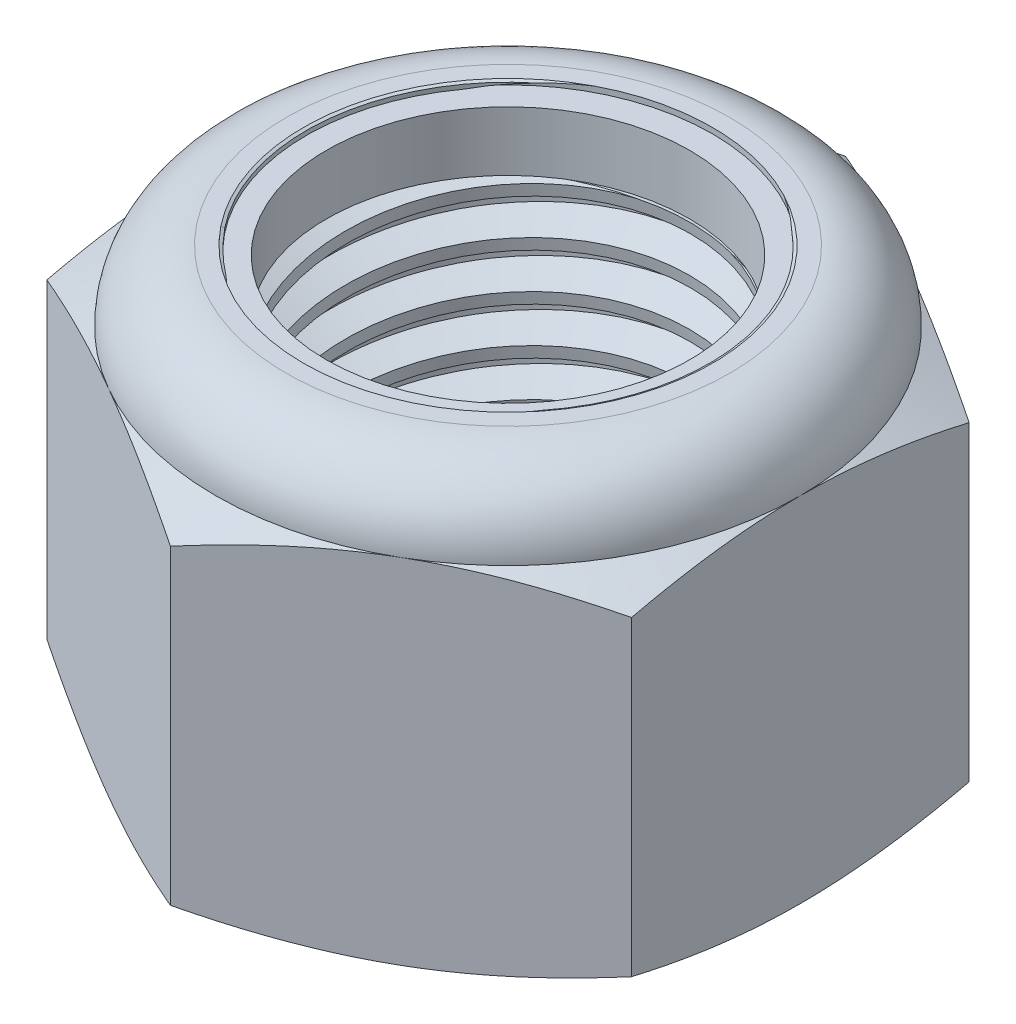
SolidWorks part; units mm, degrees
ref_plane "Front" through (0, 0, 0) normal (0, 0, 1) x (1, 0, 0)
ref_plane "Top" through (0, 0, 0) normal (0, 1, 0) x (1, 0, 0)
ref_plane "Right" through (0, 0, 0) normal (1, 0, 0) x (0, 0, -1)
sketch "Sketch1" plane through (0, 0, 0) normal (0, 1, 0) x (1, 0, 0)
  line L1 (0, 9.1654) -> (-7.9375, 4.5827)
  line L2 (-7.9375, 4.5827) -> (-7.9375, -4.5827)
  line L3 (-7.9375, -4.5827) -> (0, -9.1654)
  line L4 (0, -9.1654) -> (7.9375, -4.5827)
  line L5 (7.9375, -4.5827) -> (7.9375, 4.5827)
  line L6 (7.9375, 4.5827) -> (0, 9.1654)
  circle A0 centre (0, 0) radius 7.9375 construction
  dimension "Hex Flats" = 15.875
extrude "Extrude1" add sketch "Sketch1" along normal blind 11.5094
sketch "Sketch2" plane through (0, 0, 0) normal (1, 0, 0) x (0, 0, -1)
  line L0 (-5.5499, 0) -> (-5.5499, 11.5094) construction
  line L1 (0, 0) -> (5.5499, 0)
  line L2 (0, 0) -> (0, 11.5094)
  line L3 (0, 11.5094) -> (5.5499, 11.5094)
  line L4 (5.5499, 0) -> (5.5499, 11.5094)
  line L5 (-4.5827, 11.5094) -> (4.5827, 11.5094) construction
  line L7 (0, -5.5499) -> (0, 0) construction
  dimension "Thread Dia" = 11.0998
revolve "Revolve1" add sketch "Sketch2" angle 360 about L7
sketch "Sketch3" plane through (0, 0, 0) normal (1, 0, 0) x (0, 0, -1)
  line L0 (5.5499, 11.5094) -> (-5.5499, 11.5094) construction
  line L1 (-5.5499, 11.5094) -> (-5.5499, 10.2394) construction
  line L2 (-5.5499, 10.2394) -> (5.5499, 11.5094) construction
  line L3 (5.5499, 11.5094) -> (5.5679, 11.3517) construction
  line L4 (5.5679, 11.3517) -> (5.6943, 10.2476)
  line L5 (5.6943, 10.2476) -> (4.9662, 10.5638)
  line L6 (4.9662, 10.5638) -> (4.9301, 10.8792)
  line L7 (4.9301, 10.8792) -> (5.5679, 11.3517)
  line L8 (4.9482, 10.7215) -> (5.6311, 10.7996) construction
  line L9 (5.5499, 11.5094) -> (5.5499, 10.7903) construction
  line L10 (5.5499, 10.7903) -> (-5.5499, 9.5203) construction
  line L11 (-5.5499, 9.5203) -> (-5.5499, 10.2394) construction
  line L12 (-0.1549, 11.5094) -> (0.1549, 8.8013) construction
  line L13 (-5.5499, 0) -> (-5.5499, 11.5094) construction
  line L14 (0, 11.5094) -> (5.5499, 11.5094) construction
  line L15 (5.5499, 0) -> (5.5499, 11.5094) construction
  point P13 (0, 10.1553)
  dimension "D1" = 0.1588
  dimension "D2" = 0.3175
  dimension "Thread Pitch" = 1.27
  dimension "D4" = 60
  dimension "D5" = 1.27
revolve "Cut-Revolve1" cut sketch "Sketch3" angle 360 about L12
pattern_linear "LPattern1" count 9 spacing 1.27 along (0, -1, 0) count 2 spacing 1.27 along (0, 1, 0) of "Cut-Revolve1"
sketch "Sketch4" plane through (0, 0, 0) normal (1, 0, 0) x (0, 0, -1)
  line L0 (0, 11.5094) -> (5.5499, 11.5094)
  line L1 (5.5499, 11.5094) -> (4.9301, 11.2204)
  line L2 (4.9301, 11.2204) -> (4.9301, 0.289)
  line L3 (4.9301, 0.289) -> (5.5499, 0)
  line L4 (5.5499, 0) -> (0, 0)
  line L5 (0, 0) -> (0, 11.5094)
  line L6 (5.5499, 0) -> (5.5499, 11.5094) construction
  line L7 (0, 11.5094) -> (5.5499, 11.5094) construction
  line L8 (0, 0) -> (5.5499, 0) construction
  line L9 (0, 0) -> (0, 11.5094) construction
  line L10 (0, 11.5094) -> (0, 12.1932) construction
  dimension "D1" = 25
revolve "Cut-Revolve2" cut sketch "Sketch4" angle 360 about L10
combine bodies "Combine1" operation type subtract main body 112 bodies to subtract 111
sketch "Sketch5" plane through (0, 0, 0) normal (1, 0, 0) x (0, 0, -1)
  line L0 (0, 0) -> (7.9375, 0)
  line L1 (7.9375, 0) -> (9.1654, 0.5726)
  line L2 (9.1654, 0.5726) -> (9.1654, 9.0186)
  line L3 (9.1654, 9.0186) -> (7.9375, 9.5911)
  line L4 (6.0193, 11.5094) -> (6.0193, 12.7794)
  line L5 (6.0193, 12.7794) -> (10.4354, 12.7794)
  line L6 (10.4354, 12.7794) -> (10.4354, -1.27)
  line L7 (10.4354, -1.27) -> (0, -1.27)
  line L8 (0, -1.27) -> (0, 0)
  line L9 (7.9375, 9.5911) -> (7.9375, 0) construction
  line L10 (0, 0) -> (5.5499, 0) construction
  line L13 (9.1654, 4.7956) -> (10.4354, 4.7956) construction
  line L14 (9.1654, 11.5094) -> (9.1654, 0) construction
  line L15 (0, 0) -> (0, 12.7794) construction
  line L20 (0, 12.7794) -> (6.0193, 12.7794) construction
  line L22 (0, 11.5094) -> (5.5499, 11.5094) construction
  arc A0 (7.9375, 9.5911) -> (6.0193, 11.5094) centre (6.0193, 9.5911) ccw
  dimension "D1" = 25
  dimension "D2" = 1.27
  dimension "D3" = 11.5094
  dimension "D4" = 1.9182
revolve "Cut-Revolve3" cut sketch "Sketch5" angle 360 about L15
sketch "Sketch6" plane through (0, 0, 0) normal (1, 0, 0) x (0, 0, -1)
  line L0 (0, 9.5911) -> (7.7851, 9.5911)
  line L1 (6.0193, 11.357) -> (5.4747, 11.357)
  line L2 (0, 12.7794) -> (0, 9.5911)
  line L3 (5.4747, 12.7794) -> (0, 12.7794)
  line L4 (0, 12.7794) -> (6.0193, 12.7794) construction
  line L5 (0, 0) -> (0, 12.7794) construction
  line L6 (0, 12.7794) -> (0, 44.323) construction
  line L7 (5.4747, 11.357) -> (5.4747, 12.7794)
  line L8 (6.0193, 11.5094) -> (6.0193, 11.357) construction
  line L9 (5.4747, 11.357) -> (4.9301, 11.357) construction
  line L10 (4.9301, 11.357) -> (4.9301, 11.2204) construction
  arc A0 (7.7851, 9.5911) -> (6.0193, 11.357) centre (6.0193, 9.5911) ccw
  arc A1 (7.9375, 9.5911) -> (6.0193, 11.5094) centre (6.0193, 9.5911) ccw construction
  dimension "D1" = 0.1524
revolve "Cut-Revolve4" cut sketch "Sketch6" angle 360 about L6
sketch "Sketch7" plane through (0, 0, 0) normal (1, 0, 0) x (0, 0, -1)
  line L0 (4.9301, 9.6673) -> (7.7072, 9.6673)
  line L1 (6.0193, 11.2808) -> (4.9301, 11.2808)
  line L2 (4.9301, 11.2808) -> (4.9301, 9.6673)
  line L3 (4.9301, 9.6673) -> (0, 9.6673) construction
  line L4 (0, 9.6673) -> (0, 11.2808) construction
  line L5 (0, 11.2808) -> (4.9301, 11.2808) construction
  line L6 (4.9301, 9.6673) -> (4.9301, 9.5911) construction
  line L7 (0, 9.5911) -> (7.7851, 9.5911) construction
  line L8 (6.0193, 11.2808) -> (6.0193, 11.357) construction
  arc A0 (7.7072, 9.6673) -> (6.0193, 11.2808) centre (6.0193, 9.5911) ccw
  arc A2 (7.7851, 9.5911) -> (6.0193, 11.357) centre (6.0193, 9.5911) ccw construction
  dimension "D1" = 0.0762
revolve "Revolve2" add sketch "Sketch7" angle 360 about L4
equation "\"D1@Sketch3\"=\"Thread Pitch@Sketch3\"/8"
equation "\"D2@Sketch3\"=\"Thread Pitch@Sketch3\"/4"
equation "\"D5@Sketch3\"=\"Thread Pitch@Sketch3\""
equation "\"D4@LPattern1\"=\"Thread Pitch@Sketch3\""
equation "\"D3@LPattern1\"=\"Thread Pitch@Sketch3\""
equation "\"D1@LPattern1\"=\"Height@Extrude1\"/\"Thread Pitch@Sketch3\""
equation "\"D4@Sketch5\"=\"Height@Extrude1\"/6"
